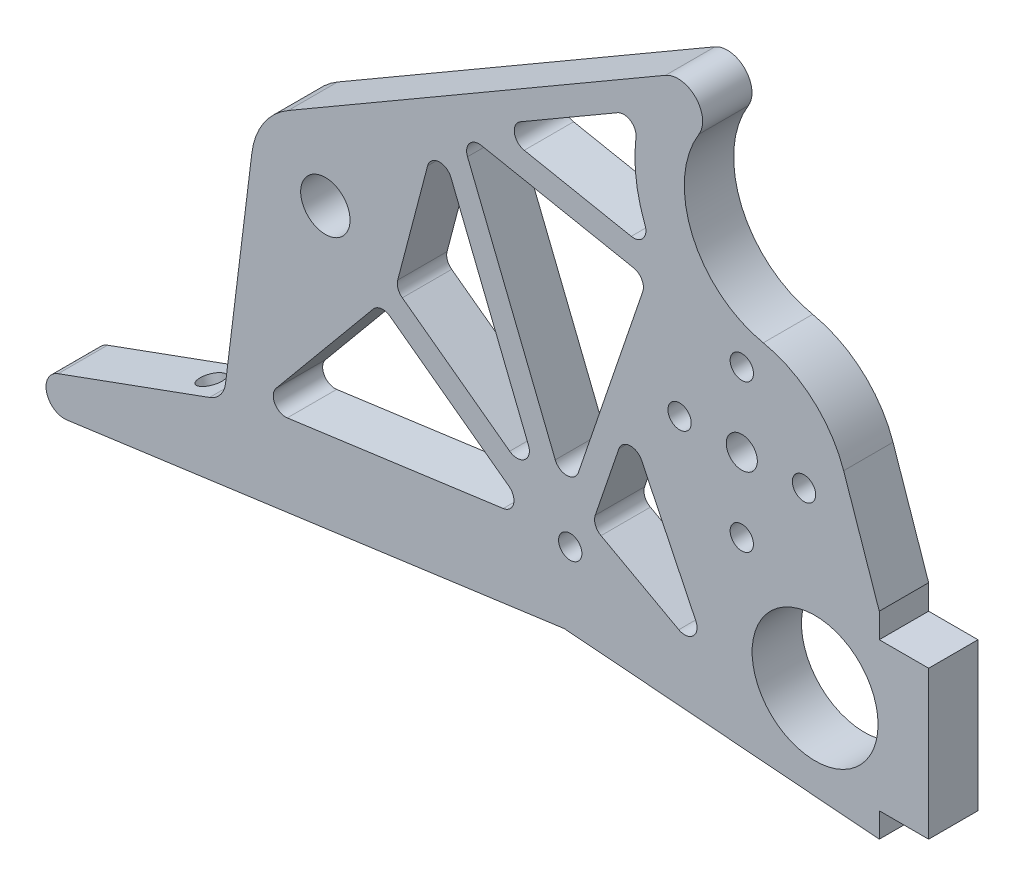
SolidWorks part; units mm, degrees
ref_plane "Front Plane" through (0, 0, 0) normal (0, 0, 1) x (1, 0, 0)
ref_plane "Top Plane" through (0, 0, 0) normal (0, 1, 0) x (1, 0, 0)
ref_plane "Right Plane" through (0, 0, 0) normal (1, 0, 0) x (0, 0, -1)
sketch "Sketch1" plane through (0, 0, 0) normal (0, 0, 1) x (1, 0, 0)
  line L0 (12.2605, 58.6546) -> (-36.2799, 30.4615)
  line L1 (0, -55) -> (0, 55) construction
  line L2 (39.751, 9.525) -> (46.101, 9.525)
  line L3 (39.751, 9.525) -> (39.751, -9.525) construction
  line L4 (39.751, -9.525) -> (46.101, -9.525)
  line L5 (46.101, 9.525) -> (46.101, -9.525)
  line L6 (14.0686, 21.567) -> (30.0686, 21.567) construction
  line L7 (22.0686, 31.067) -> (22.0686, 12.067) construction
  line L8 (39.751, 9.525) -> (39.751, 12.7)
  line L9 (39.751, -9.525) -> (39.751, -12.7)
  line L10 (-36.9877, 14.4425) -> (-5.4917, -7.7825)
  line L11 (39.751, -12.7) -> (-0.7513, -9.4953)
  line L12 (-18.0656, 110.4417) -> (26016.8979, -39640.6484) construction
  line L14 (22.0686, 21.567) -> (34.7171, 29.8512) construction
  line L15 (39.751, 12.7) -> (35.1696, 26.0597)
  line L16 (22.0686, 21.567) -> (23.8659, 17.4552)
  line L17 (23.8659, 17.4552) -> (27.6159, 8.8765) construction
  line L18 (27.6159, 8.8765) -> (28.2517, 7.4219)
  line L19 (28.2517, 7.4219) -> (31.496, 0) construction
  circle A2 centre (31.496, 0) radius 19.05 construction
  circle A3 centre (-31.496, 0) radius 19.05 construction
  circle A4 centre (-31.496, 22.225) radius 38.1 construction
  circle A5 centre (0, 0) radius 1.5
  circle A6 centre (22.0686, 31.067) radius 1.5
  circle A7 centre (30.0686, 21.567) radius 1.5
  circle A8 centre (22.0686, 12.067) radius 1.5
  circle A9 centre (14.0686, 21.567) radius 1.5
  circle A11 centre (-31.496, 22.225) radius 3.175
  arc A12 (-36.2799, 30.4615) -> (-36.9877, 14.4425) centre (-31.496, 22.225) ccw
  arc A19 (35.1696, 26.0597) -> (24.8346, 35.138) centre (22.0686, 21.567) ccw
  arc A20 (16.5583, 54.2437) -> (12.2605, 58.6546) centre (13.8552, 55.9091) ccw
  arc A21 (-5.4917, -7.7825) -> (-0.7513, -9.4953) centre (0, 0) ccw
  arc A22 (16.5583, 54.2437) -> (24.8346, 35.138) centre (27.371, 47.5822) ccw
  arc A23 (-36.9877, 14.4425) -> (-36.2799, 30.4615) centre (-31.496, 22.225) ccw construction
  circle A31 centre (22.0686, 21.567) radius 2
  arc A33 (4.086, 8.6041) -> (-5.4917, -7.7825) centre (0, 0) ccw construction
  arc A34 (-0.7513, -9.4953) -> (4.086, 8.6041) centre (0, 0) ccw construction
  arc A35 (24.8346, 35.138) -> (15.0556, 9.6238) centre (22.0686, 21.567) ccw construction
  arc A36 (15.0556, 9.6238) -> (35.1696, 26.0597) centre (22.0686, 21.567) ccw construction
  circle A37 centre (31.496, 0) radius 8.1
  point P2 (33.6547, 29.1554)
  point P10 (46.101, 0)
  point P13 (-31.496, -19.05)
  point P24 (-31.496, -15.875)
  point P26 (22.0686, 21.567)
  point P29 (22.0686, 21.567)
  point P37 (42.926, -9.525)
  dimension "D7" = 38.1
  dimension "D8" = 76.2
  dimension "D11" = 3
  dimension "D13" = 3
  dimension "D14" = 27.7
  dimension "D16" = 6.35
  dimension "D17" = 19.05
  dimension "D21" = 6.35
  dimension "D22" = 1.5875
  dimension "D23" = 16.2
  dimension "D25" = 56.134
  dimension "D26" = 4
  dimension "D19" = 19.05
  dimension "D24" = 12.7
  dimension "D3" = 19.05
  dimension "D4" = 6.35
  dimension "D5" = 11.43
  dimension "D6" = 62.992
  dimension "D9" = 3.175
  dimension "D10" = 19
  dimension "D12" = 16
  dimension "D15" = 1.27
  dimension "D18" = 53.5686
  dimension "D20" = 3.175
extrude "Boss-Extrude1" add sketch "Sketch1" along normal mid plane 6.35 contours L10 L11 L9 L4 L5 L2 L8 A12 A20 A6 A7 A8 A9 A11 region at (3.5012, 18.9329, 0)
sketch "Sketch2" plane through (0, 0, 3.175) normal (0, 0, 1) x (1, 0, 0)
  line L0 (-46.398, -6.562) -> (-65.8615, -13.6461) construction
  line L1 (-46.398, -6.562) -> (-65.8615, -13.6461)
  line L2 (-44.3329, -3.9682) -> (-40.949, 23.3941)
  line L3 (-64.7244, -18.2431) -> (-0.7513, -9.4953)
  line L4 (-36.9877, 14.4425) -> (-5.4917, -7.7825) construction
  line L5 (-36.9877, 14.4425) -> (-5.4917, -7.7825)
  arc A0 (-65.8615, -13.6461) -> (-64.8428, -18.2563) centre (-65.0471, -15.8838) ccw construction
  arc A1 (-65.8615, -13.6461) -> (-64.7244, -18.2431) centre (-65.0471, -15.8838) ccw
  arc A2 (-5.4917, -7.7825) -> (-0.7513, -9.4953) centre (0, 0) ccw construction
  arc A3 (-46.398, -6.562) -> (-44.3329, -3.9682) centre (-47.4839, -3.5785) ccw
  arc A4 (-36.2799, 30.4615) -> (-36.9877, 14.4425) centre (-31.496, 22.225) ccw construction
  arc A5 (-5.4917, -7.7825) -> (-0.7513, -9.4953) centre (0, 0) ccw
  arc A6 (-40.949, 23.3941) -> (-36.9877, 14.4425) centre (-31.496, 22.225) ccw
  dimension "D1" = 3.175
extrude "Boss-Extrude2" add sketch "Sketch2" against normal up to surface (6.35 mm away) up to face at (39.596, 0, -3.175)
sketch "Sketch3" plane through (-3.3185, 9.1176, 0) normal (-0.342, 0.9397, 0) x (0.9397, 0.342, 0)
  line L0 (-45.8442, 3.175) -> (-45.8442, -3.175) construction
  line L1 (-49.0192, 0) -> (-45.8442, 0) construction
  circle A0 centre (-49.0192, 0) radius 1.5
  dimension "D1" = 3
  dimension "D2" = 3.175
extrude "Cut-Extrude1" cut sketch "Sketch3" against normal blind 6
sketch "Sketch4" plane through (0, 0, -3.175) normal (0, 0, -1) x (-1, 0, 0)
  line L0 (-9.1632, 53.184) -> (10.0553, 42.0215)
  line L1 (14.2982, 39.5572) -> (0.3283, 4.7512)
  line L2 (3.2899, 3.4435) -> (17.1256, 37.915)
  line L4 (-9.9151, 34.8034) -> (0.3283, 4.7512)
  line L8 (-31.496, 0) -> (-18.317, -4.6342) construction
  line L9 (-12.2605, 58.6546) -> (36.2799, 30.4615) construction
  line L10 (-12.2605, 58.6546) -> (36.2799, 30.4615)
  line L11 (-9.1632, 53.184) -> (-7.5686, 55.9295) construction
  line L12 (-7.5034, 17.6989) -> (-18.317, -4.6342)
  line L13 (17.1256, 37.915) -> (22.4622, 17.5758)
  line L14 (3.2899, 3.4435) -> (22.4622, 17.5758)
  line L15 (24.382, 14.9713) -> (4.7372, 0.4906)
  line L16 (4.2529, 2.1435) -> (31.496, 22.225) construction
  line L17 (14.8795, 7.9668) -> (12.9597, 10.5713) construction
  line L18 (4.7372, 0.4906) -> (40.4309, -4.3902)
  line L19 (0.7513, -9.4953) -> (64.7244, -18.2431) construction
  line L20 (14.2982, 39.5572) -> (-9.9151, 34.8034)
  line L21 (-10.9685, 37.894) -> (10.0553, 42.0215)
  line L22 (-0.4566, 39.9577) -> (0.1667, 36.7827) construction
  line L23 (10.0553, 42.0215) -> (14.2982, 39.5572) construction
  line L25 (10.316, 20.949) -> (7.3132, 22.1542) construction
  line L26 (-10.9685, 37.894) -> (-9.9151, 34.8034) construction
  line L28 (24.382, 14.9713) -> (40.4309, -4.3902)
  line L29 (-8.4524, 45.3485) -> (-14.7586, 46.093) construction
  line L31 (46.398, -6.562) -> (40.4309, -4.3902) construction
  line L32 (65.8615, -13.6461) -> (46.398, -6.562) construction
  line L33 (-18.317, -4.6342) -> (-2.787, 3.8619)
  line L34 (-2.787, 3.8619) -> (-7.5034, 17.6989)
  line L35 (-2.4966, 13.039) -> (-5.5592, 11.9951) construction
  line L36 (-39.751, -12.7) -> (0.7513, -9.4953) construction
  arc A1 (-10.9685, 37.894) -> (-9.1632, 53.184) centre (-27.371, 47.5822) ccw
  arc A2 (-24.8346, 35.138) -> (-16.5583, 54.2437) centre (-27.371, 47.5822) ccw construction
  circle A3 centre (-31.496, 0) radius 8.1 construction
  circle A4 centre (-31.496, 0) radius 8.1
  circle A5 centre (0, 0) radius 4.7625 construction
  arc A6 (23.3177, 16.1966) -> (24.382, 14.9713) centre (31.496, 22.225) ccw construction
  arc A7 (22.4622, 17.5758) -> (23.3177, 16.1966) centre (31.496, 22.225) ccw construction
  circle A8 centre (-14.0686, 21.567) radius 1.5 construction
  point P34 (13.9196, 9.269)
  point P48 (40.6311, -4.3902)
  point P49 (-2.7915, 3.8586)
  point P50 (-7.9655, 19.0548)
  dimension "D5" = 9.525
  dimension "D11" = 7.62
  dimension "D1" = 6.35
  dimension "D2" = 3.175
  dimension "D3" = 10.16
  dimension "D4" = 31.75
  dimension "D6" = 3.175
  dimension "D7" = 6.35
  dimension "D8" = 22.225
  dimension "D9" = 13.97
  dimension "D10" = 6.35
extrude "Cut-Extrude2" cut sketch "Sketch4" against normal through all and the other way through all contours A1 L21 L0 | L1 L20 L4 | L2 L14 | L15 | L33 L34 L12 region at (2.6316, 44.2349, -3.175) region at (-1.5705, 26.3706, -3.175) region at (-14.2926, 19.6448, -3.175) region at (9.5358, 5.6422, -3.175) region at (-23.1834, 3.6906, -3.175)
fillet "Fillet1" radius 1.5875 15 edges at (-10.0553, 42.0215, 0) (9.1632, 53.184, 0) (9.9151, 34.8034, 0) (-14.2982, 39.5572, 0) (-22.4622, 17.5758, 0) (-17.1256, 37.915, 0) (-24.382, 14.9713, 0) (-3.2899, 3.4435, 0) (-0.3283, 4.7512, 0) (10.9685, 37.894, 0) (2.787, 3.8619, 0) (7.5034, 17.6989, 0) (18.317, -4.6342, 0) (-40.4309, -4.3902, 0) (-4.7372, 0.4906, 0)
